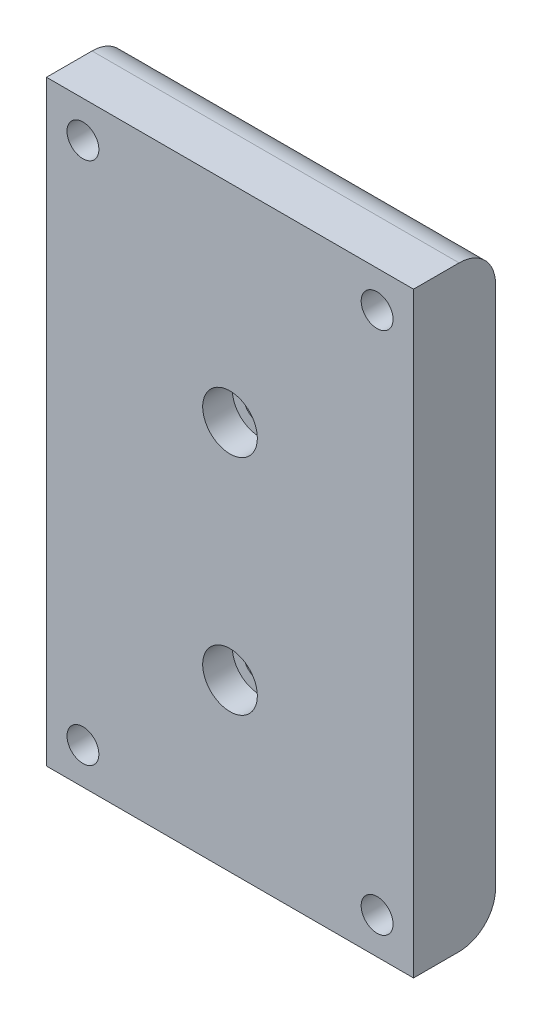
SolidWorks part; units mm, degrees
ref_plane "Front Plane" through (0, 0, 0) normal (0, 0, 1) x (1, 0, 0)
ref_plane "Top Plane" through (0, 0, 0) normal (0, 1, 0) x (1, 0, 0)
ref_plane "Right Plane" through (0, 0, 0) normal (1, 0, 0) x (0, 0, -1)
sketch "Sketch1" plane through (0, 0, 0) normal (0, 0, 1) x (1, 0, 0)
  line L1 (0, 0) -> (40.3, 0)
  line L2 (0, 0) -> (0, 65.5)
  line L3 (0, 65.5) -> (40.3, 65.5)
  line L4 (40.3, 0) -> (40.3, 65.5)
  dimension "D1" = 40.3
  dimension "D2" = 65.5
extrude "Boss-Extrude1" add sketch "Sketch1" along normal blind 9
sketch "Sketch2" plane through (0, 0, 0) normal (0, 0, -1) x (-1, 0, 0)
  line L0 (-40.3, 32.75) -> (0, 32.75) construction
  line L1 (-40.3, 0) -> (-40.3, 65.5) construction
  line L2 (0, 65.5) -> (0, 0) construction
  line L3 (-40.3, 42.75) -> (0, 42.75) construction
  line L4 (-20.15, 42.75) -> (-20.15, 18.25) construction
  line L5 (-24.65, 18.25) -> (-24.65, 32.0846)
  line L6 (-15.65, 18.25) -> (-15.65, 32.0846)
  arc A0 (-13.7056, 38.0098) -> (-26.5944, 38.0098) centre (-20.15, 42.75) ccw
  arc A1 (-24.65, 18.25) -> (-15.65, 18.25) centre (-20.15, 18.25) ccw
  arc A2 (-15.65, 32.0846) -> (-13.7056, 38.0098) centre (-5.65, 32.0846) cw
  arc A3 (-24.65, 32.0846) -> (-26.5944, 38.0098) centre (-34.65, 32.0846) ccw
  point P11 (-20.15, 42.75)
  dimension "D2" = 16
  dimension "D3" = 9
  dimension "D5" = 10
  dimension "D4" = 24.5
  dimension "D1" = 10
extrude "Cut-Extrude2" cut sketch "Sketch2" against normal blind 4.5
sketch "Sketch3" plane through (0, 0, 4.5) normal (0, 0, -1) x (-1, 0, 0)
  line L0 (-20.15, 42.75) -> (-20.15, 22.25) construction
  line L1 (-20.15, 22.25) -> (-20.15, 18.25) construction
  line L2 (-23.15, 18.25) -> (-23.15, 22.25)
  line L3 (-17.15, 22.25) -> (-17.15, 18.25)
  arc A0 (-17.15, 22.25) -> (-23.15, 22.25) centre (-20.15, 22.25) ccw
  arc A1 (-23.15, 18.25) -> (-17.15, 18.25) centre (-20.15, 18.25) ccw
  circle A2 centre (-20.15, 22.25) radius 1.75
  circle A3 centre (-20.15, 18.25) radius 1.75
  circle A4 centre (-20.15, 42.75) radius 1.75
  dimension "D2" = 6
  dimension "D4" = 3.5
  dimension "D5" = 3.5
  dimension "D1" = 20.5
  dimension "D3" = 4
extrude "Cut-Extrude5" cut sketch "Sketch3" against normal through all contours A3 | A4 region at (20.15, 18.25, 4.5) region at (20.15, 42.75, 4.5)
sketch "Sketch5" plane through (0, 0, 9) normal (0, 0, 1) x (1, 0, 0)
  circle A0 centre (20.15, 18.25) radius 3
  circle A1 centre (20.15, 42.75) radius 3
  dimension "D1" = 6
extrude "Cut-Extrude6" cut sketch "Sketch5" against normal blind 3.25
fillet "Fillet1" radius 4 2 edges at (20.15, 0, 0) (20.15, 65.5, 0)
sketch "Sketch6" plane through (0, 0, 0) normal (0, 0, -1) x (-1, 0, 0)
  line L0 (-4, 61.5) -> (-4, 4) construction
  line L1 (-40.3, 65.5) -> (0, 65.5) construction
  line L2 (-40.3, 65.5) -> (-40.3, 0) construction
  line L3 (-40.3, 0) -> (0, 0) construction
  line L4 (0, 65.5) -> (0, 0) construction
  line L5 (-36.3, 4) -> (-4, 4) construction
  line L6 (-36.3, 61.5) -> (-36.3, 4) construction
  line L7 (-36.3, 61.5) -> (-4, 61.5) construction
  circle A0 centre (-36.3, 61.5) radius 1.75
  circle A1 centre (-4, 61.5) radius 1.75
  circle A2 centre (-4, 4) radius 1.75
  circle A3 centre (-36.3, 4) radius 1.75
  line M16 (-40.3, 4) -> (0, 4)
  dimension "D2" = 3.5
  dimension "D1" = 4
extrude "Cut-Extrude7" cut sketch "Sketch6" against normal through all contours A2 M16 | A2 M16 | A3 M16 | A3 M16 | A0 | A1 region at (4, 4.7427, 0) region at (36.3, 3.2573, 0) region at (36.3, 4.7427, 0) region at (4, 3.2573, 0)
sketch "Sketch7" plane through (0, 0, 0) normal (0, 0, -1) x (-1, 0, 0)
  circle A0 centre (-36.3, 61.5) radius 3
  circle A1 centre (-4, 61.5) radius 3
  circle A2 centre (-4, 4) radius 3
  circle A3 centre (-36.3, 4) radius 3
  dimension "D1" = 6
extrude "Cut-Extrude8" cut sketch "Sketch7" against normal blind 3
